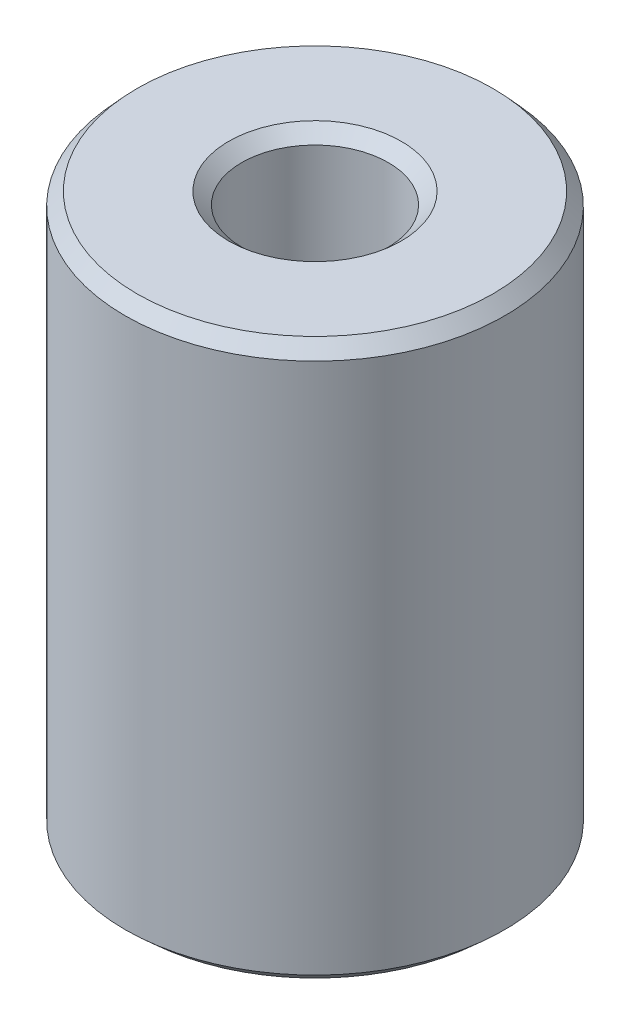
SolidWorks part; units mm, degrees
ref_plane "Front Plane" through (0, 0, 0) normal (0, 0, 1) x (1, 0, 0)
ref_plane "Top Plane" through (0, 0, 0) normal (0, 1, 0) x (1, 0, 0)
ref_plane "Right Plane" through (0, 0, 0) normal (1, 0, 0) x (0, 0, -1)
sketch "Sketch1" plane through (0, 0, 0) normal (0, 1, 0) x (1, 0, 0)
  circle A0 centre (0, 0) radius 17.5
  dimension "SLEEVE_OD" = 35
extrude "Boss-Extrude1" add sketch "Sketch1" along normal blind 51.3254
sketch "Sketch2" plane through (0, 0, 0) normal (0, 1, 0) x (1, 0, 0)
  circle A0 centre (0, 0) radius 6.7589
  dimension "BORE_D" = 13.5178
extrude "Cut-Extrude1" cut sketch "Sketch2" along normal through all
chamfer "Chamfer1" distance 1.2053 angle 42.16 4 edges at (0, 51.3254, 6.7589) (0, 0, 6.7589) (0, 0, 17.5) (0, 51.3254, 17.5) first distance on face at (0, 51.3254, 6.7589) first distance on face at (0, 0, 6.7589) first distance on face at (0, 51.3254, 17.5)
